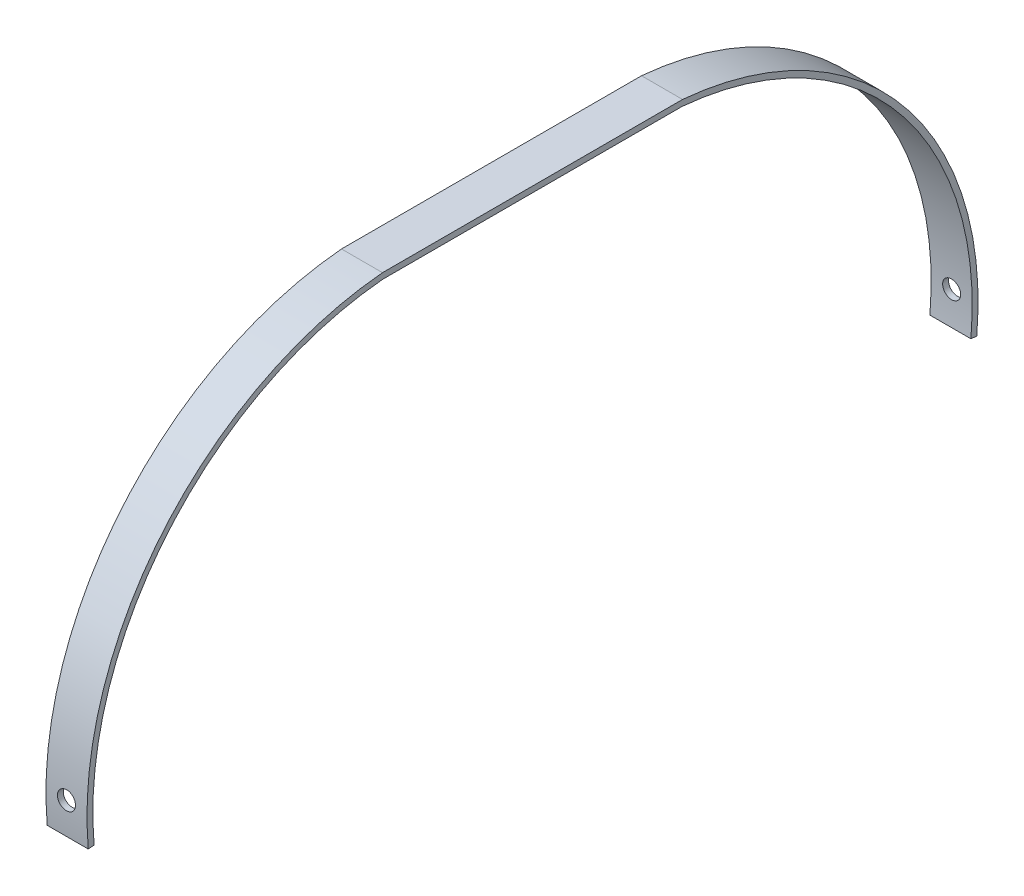
SolidWorks part; units mm, degrees
ref_plane "Front Plane" through (0, 0, 0) normal (0, 0, 1) x (1, 0, 0)
ref_plane "Top Plane" through (0, 0, 0) normal (0, 1, 0) x (1, 0, 0)
ref_plane "Right Plane" through (0, 0, 0) normal (1, 0, 0) x (0, 0, -1)
sketch "Sketch1" plane through (0, 0, 0) normal (1, 0, 0) x (0, 0, -1)
  line L0 (-65, -1.27) -> (-65, -151.27) construction
  line L1 (-65, -1.27) -> (65, -1.27)
  line L2 (-65, -1.27) -> (-65, 1.27)
  line L3 (-65, 1.27) -> (65, 1.27)
  line L4 (65, -1.27) -> (65, 1.27)
  line L5 (-65, -1.27) -> (65, 1.27) construction
  line L6 (-65, 1.27) -> (65, -1.27) construction
  line L7 (-65, -151.27) -> (-192.5, -151.27) construction
  line L8 (0, 0) -> (0, -148.537) construction
  line L9 (-189.9701, -151.0438) -> (-192.5, -151.27)
  line L10 (65, -151.27) -> (192.5, -151.27) construction
  line L11 (189.9701, -151.0438) -> (192.5, -151.27)
  arc A0 (-65, 1.27) -> (-192.5, -151.27) centre (-52.48, -138.75) ccw
  arc A1 (-64.7738, -1.2599) -> (-189.9701, -151.0438) centre (-52.48, -138.75) ccw
  arc A2 (64.7738, -1.2599) -> (189.9701, -151.0438) centre (52.48, -138.75) cw
  arc A3 (65, 1.27) -> (192.5, -151.27) centre (52.48, -138.75) cw
  point P0 (0, 0)
  dimension "D1" = 130
  dimension "D2" = 2.54
  dimension "D3" = 150
  dimension "D4" = 127.5
  dimension "D5" = 2.54
extrude "Boss-Extrude1" add sketch "Sketch1" along normal blind 17.78 contours A1 L1 L2 A0 L9 | L1 L4 L3 L2 | A3 L4 L1 A2 L11 region at (0, 0, 0) region at (0, -48.989, 159.9586) region at (0, 0, -66.9924)
sketch "Sketch2" plane through (0, 0, 0) normal (0, 0, 1) x (1, 0, 0)
  line L0 (0, 0) -> (8.89, 0) construction
  line L1 (8.89, 0) -> (8.89, -137.16) construction
  circle A0 centre (8.89, -137.16) radius 3.9142
  dimension "D1" = 8.89
  dimension "D2" = 137.16
extrude "Cut-Extrude1" cut sketch "Sketch2" against normal through all both and the other way through all
